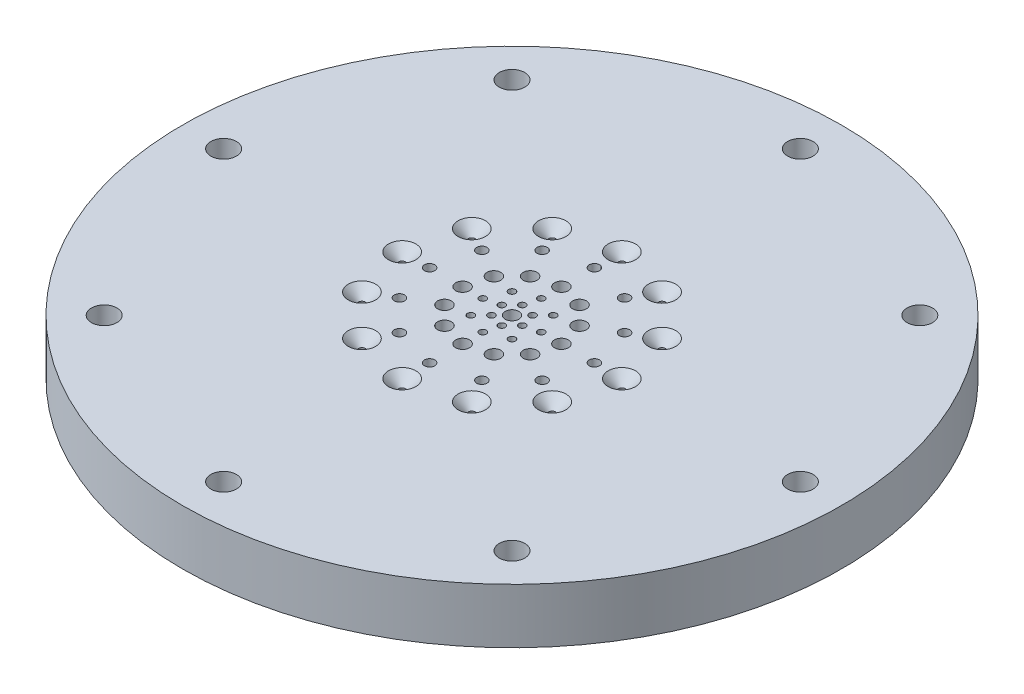
SolidWorks part; units mm, degrees
ref_plane "Front Plane" through (0, 0, 0) normal (0, 0, 1) x (1, 0, 0)
ref_plane "Top Plane" through (0, 0, 0) normal (0, 1, 0) x (1, 0, 0)
ref_plane "Right Plane" through (0, 0, 0) normal (1, 0, 0) x (0, 0, -1)
sketch "Sketch1" plane through (0, 0, 0) normal (0, 1, 0) x (1, 0, 0)
  circle A0 centre (0, 0) radius 38.1
  dimension "D1" = 76.2
extrude "Boss-Extrude1" add sketch "Sketch1" along normal blind 6.35
sketch "Sketch2" plane through (0, 0, 0) normal (0, -1, 0) x (1, 0, 0)
  circle A0 centre (0, 0) radius 33.3375
  circle A1 centre (0, 33.3375) radius 0.762
  dimension "D1" = 66.675
hole_wizard "CBORE for #4 Button Head Cap Screw1" positions "Sketch5" profile "Sketch4" counterbore size "#4" standard "ANSI Inch" end condition through all
sketch "Sketch5" plane through (0, 0, 0) normal (0, -1, 0) x (-1, 0, 0)
  point P0 (0, -33.3375)
sketch "Sketch4" plane through (0, 0, 33.3375) normal (1, 0, 0) x (0, 0, -1)
  line L0 (0, 0) -> (0, 6.35)
  line L1 (0, 6.35) -> (1.4732, 6.35)
  line L3 (1.4732, 6.35) -> (1.4732, 2.8448)
  line L4 (1.4732, 2.8448) -> (2.413, 2.8448)
  line L5 (2.413, 2.8448) -> (2.413, 0)
  line L7 (2.413, 0) -> (0, 0)
  line L11 (0, -6.35) -> (0, 107.95) construction
  dimension "Thru Hole Dia." = 2.9464
  dimension "Thru Hole Depth" = 6.35
  dimension "C'Bore Dia." = 4.826
  dimension "C'Bore Depth" = 2.8448
pattern_circular "CirPattern1" count 8 over 360 about axis through (0, 0, 0) along (0, 1, 0) of "CBORE for #4 Button Head Cap Screw1"
sketch "Sketch6" plane through (0, 6.35, 0) normal (0, 1, 0) x (1, 0, 0)
  circle A0 centre (0, 0) radius 28.575
  dimension "D1" = 57.15
sketch "Sketch7" plane through (0, 0, 0) normal (0, -1, 0) x (1, 0, 0)
  circle A0 centre (0, 12.7) radius 0.3937
  circle A1 centre (0, 9.525) radius 0.5969
  circle A2 centre (0, 5.715) radius 0.8001
  circle A3 centre (0, 0) radius 0.7937
  dimension "D1" = 0.7874
  dimension "D3" = 1.1938
  dimension "D4" = 9.525
  dimension "D5" = 1.6002
  dimension "D6" = 5.715
  dimension "D7" = 1.5875
  dimension "D2" = 12.7
extrude "Cut-Extrude1" cut sketch "Sketch7" against normal through all
pattern_circular "CirPattern3" count 12 over 360 about axis through (0, 0, 0) along (0, 1, 0) of "Cut-Extrude1"
sketch "Sketch8" plane through (0, 6.35, 0) normal (0, 1, 0) x (1, 0, 0)
  circle A0 centre (3.3688, 0) radius 0.3969
  circle A1 centre (2.3821, -2.3821) radius 0.3969
  circle A2 centre (0, -3.3688) radius 0.3969
  circle A3 centre (-2.3821, -2.3821) radius 0.3969
  circle A4 centre (-3.3688, 0) radius 0.3969
  circle A5 centre (-2.3821, 2.3821) radius 0.3969
  circle A6 centre (0, 3.3688) radius 0.3969
  circle A7 centre (2.3821, 2.3821) radius 0.3969
  point P19 (0, 0)
  dimension "D1" = 8
extrude "Cut-Extrude3" cut sketch "Sketch8" against normal up to next
sketch "Sketch9" plane through (0, 6.35, 0) normal (0, 1, 0) x (1, 0, 0)
  line L0 (0, 0) -> (2.3821, 2.3821) construction
  circle A2 centre (1.1877, 1.1877) radius 0.3969
  circle A3 centre (1.6225, -0.4347) radius 0.3969
  circle A4 centre (0.4347, -1.6225) radius 0.3969
  circle A5 centre (-1.1877, -1.1877) radius 0.3969
  circle A6 centre (-1.6225, 0.4347) radius 0.3969
  circle A7 centre (-0.4347, 1.6225) radius 0.3969
  point P18 (0, 0)
  dimension "D1" = 1.6891
  dimension "D2" = 6
extrude "Cut-Extrude4" cut sketch "Sketch9" against normal up to next
chamfer "Chamfer1" distance 1.1906 angle 45 12 edges at (6.1531, 6.35, -10.6576) (10.6576, 6.35, -6.1532) (12.3063, 6.35, 0) (10.6576, 6.35, 6.1531) (6.1532, 6.35, 10.6576) (0, 6.35, 12.3063) (-6.1531, 6.35, 10.6576) (-10.6576, 6.35, 6.1532) (-12.3063, 6.35, 0) (-10.6576, 6.35, -6.1531) (-6.1532, 6.35, -10.6576) (0, 6.35, -12.3063)
